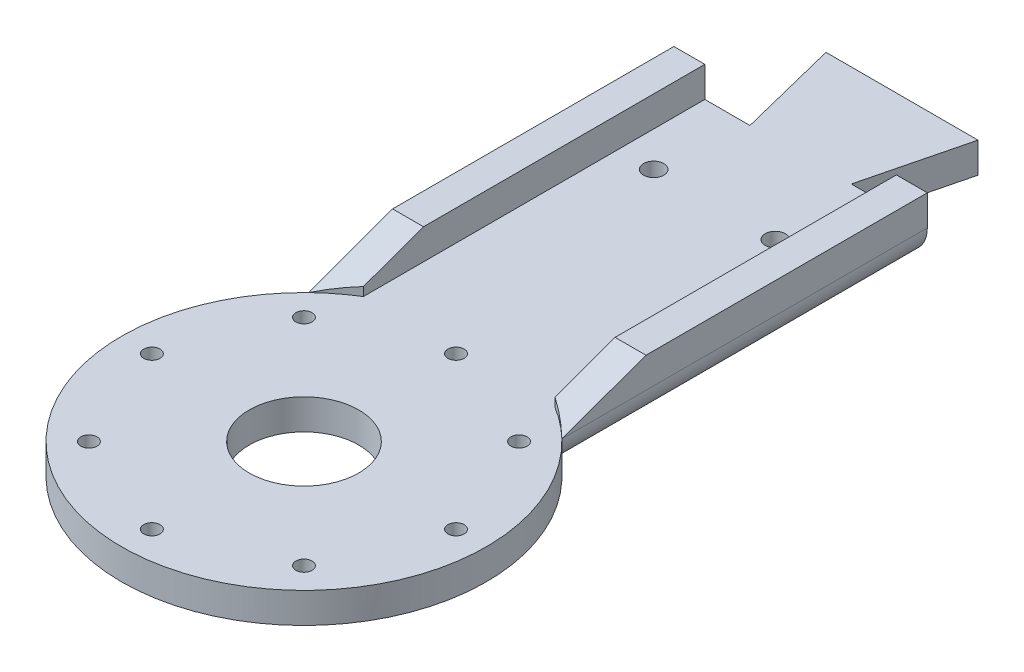
SolidWorks part; units mm, degrees
ref_plane "Alzado" through (0, 0, 0) normal (0, 0, 1) x (1, 0, 0)
ref_plane "Planta" through (0, 0, 0) normal (0, 1, 0) x (1, 0, 0)
ref_plane "Vista lateral" through (0, 0, 0) normal (1, 0, 0) x (0, 0, -1)
sketch "Croquis1" plane through (0, 0, 0) normal (0, 1, 0) x (1, 0, 0)
  line L0 (-12.2731, 28.8401) -> (-4.7731, 28.8401)
  line L4 (5.2269, 28.8401) -> (12.7269, 28.8401)
  line L5 (12.7269, 28.8401) -> (12.7269, -7.2163)
  line L6 (-12.2731, 28.8401) -> (-12.2731, -7.2163)
  line L8 (7.7269, 38.8401) -> (5.2269, 28.8401)
  line L9 (-7.2731, 38.8401) -> (7.7269, 38.8401)
  line L10 (-4.7731, 28.8401) -> (-7.2731, 38.8401)
  arc A0 (-12.2731, -7.2163) -> (12.7269, -7.2163) centre (0.2269, -20.1632) ccw
  circle A1 centre (0.2269, -20.1596) radius 5.4
  circle A2 centre (6.2269, 20.3404) radius 1
  circle A3 centre (-5.7731, 20.3404) radius 1
  circle A4 centre (0.2269, -5.1596) radius 0.8
  circle A5 centre (10.8361, -9.5541) radius 0.8
  circle A6 centre (15.2305, -20.1632) radius 0.8
  circle A7 centre (10.8361, -30.7724) radius 0.8
  circle A8 centre (0.2269, -35.1668) radius 0.8
  circle A9 centre (-10.3822, -30.7724) radius 0.8
  circle A10 centre (-14.7767, -20.1632) radius 0.8
  circle A11 centre (-10.3822, -9.5541) radius 0.8
  point P3 (0, 0)
  point P31 (0.2269, -20.1632)
  dimension "D1" = 10
  dimension "D2" = 2.5
  dimension "D5" = 7.5
extrude "Saliente-Extruir1" add sketch "Croquis1" along normal blind 3
sketch "Croquis2" plane through (0, 3, 0) normal (0, 1, 0) x (1, 0, 0)
  line L0 (0.2269, 28.8404) -> (0.2269, -45.8505) construction
  line L1 (-12.2731, 28.8401) -> (-9.2231, 28.8401)
  line L2 (-12.2731, 28.8401) -> (-12.2731, -7.2163)
  line L4 (-9.2231, 28.8401) -> (-9.2231, -4.847)
  line L6 (9.6769, 28.8401) -> (9.6769, -4.847)
  line L8 (12.7269, 28.8401) -> (12.7269, -7.2163)
  line L9 (12.7269, 28.8401) -> (9.6769, 28.8401)
  arc A0 (-9.2231, -4.847) -> (-12.2731, -7.2163) centre (0.2269, -20.1596) ccw
  arc A1 (12.7269, -7.2163) -> (9.6769, -4.847) centre (0.2269, -20.1596) ccw
  dimension "D1" = 3.05
extrude "Saliente-Extruir2" add sketch "Croquis2" along normal blind 3
sketch "Croquis3" plane through (-12.2731, 0, 0) normal (-1, 0, 0) x (0, 0, 1)
  line L0 (-1.0837, 6) -> (7.2163, 3)
  line L1 (-28.8401, 6) -> (7.2163, 6) construction
  line L2 (7.2163, 3) -> (7.2163, 6)
  line L3 (7.2163, 6) -> (-1.0837, 6)
  dimension "D1" = 8.3
extrude "Cortar-Extruir1" cut sketch "Croquis3" against normal blind 42
fillet "Redondeo1" radius 3 2 edges at (12.7269, 0, -10.8119) (-12.2731, 0, -10.8119)
